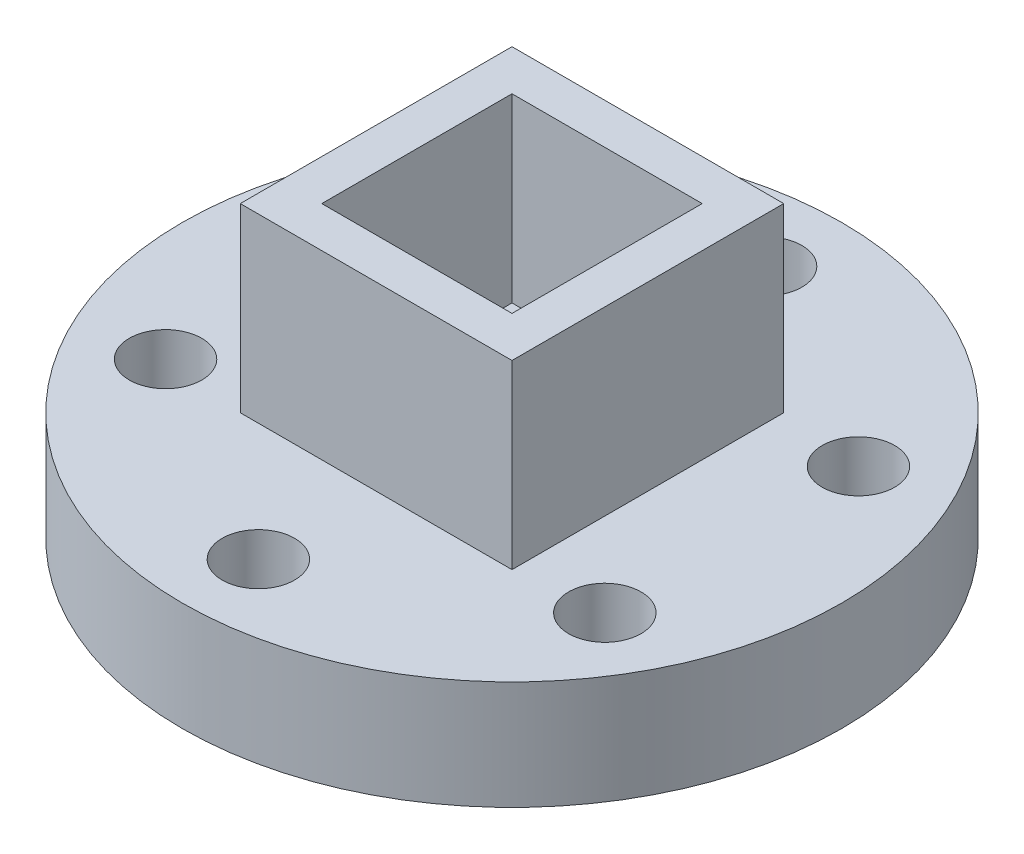
SolidWorks part; units mm, degrees
ref_plane "Front Plane" through (0, 0, 0) normal (0, 0, 1) x (1, 0, 0)
ref_plane "Top Plane" through (0, 0, 0) normal (0, 1, 0) x (1, 0, 0)
ref_plane "Right Plane" through (0, 0, 0) normal (1, 0, 0) x (0, 0, -1)
sketch "Sketch1" plane through (0, 0, 0) normal (0, 1, 0) x (1, 0, 0)
  circle A0 centre (0, 0) radius 18.2
  dimension "D1" = 36.4
extrude "Boss-Extrude1" add sketch "Sketch1" along normal blind 6 contours A0
sketch "Sketch2" plane through (0, 6, 0) normal (0, 1, 0) x (1, 0, 0)
  circle A0 centre (0, 14) radius 2
  circle A1 centre (12.1244, 7) radius 2
  circle A2 centre (12.1244, -7) radius 2
  circle A3 centre (0, -14) radius 2
  circle A4 centre (-12.1244, -7) radius 2
  circle A5 centre (-12.1244, 7) radius 2
  dimension "D1" = 14
  dimension "D2" = 6
extrude "Cut-Extrude1" cut sketch "Sketch2" against normal blind 6
sketch "Sketch3" plane through (0, 6, 0) normal (0, 1, 0) x (1, 0, 0)
  line L1 (-7.5, 7.5) -> (7.5, 7.5)
  line L2 (-7.5, 7.5) -> (-7.5, -7.5)
  line L3 (-7.5, -7.5) -> (7.5, -7.5)
  line L4 (7.5, 7.5) -> (7.5, -7.5)
  line L5 (-7.5, 7.5) -> (7.5, -7.5) construction
  line L6 (-7.5, -7.5) -> (7.5, 7.5) construction
  point P0 (0, 0)
extrude "Boss-Extrude2" add sketch "Sketch3" along normal blind 10
sketch "Sketch5" plane through (0, 16, 0) normal (0, 1, 0) x (1, 0, 0)
  line L1 (-5.25, 5.25) -> (5.25, 5.25)
  line L2 (-5.25, 5.25) -> (-5.25, -5.25)
  line L3 (-5.25, -5.25) -> (5.25, -5.25)
  line L4 (5.25, 5.25) -> (5.25, -5.25)
  line L5 (-5.25, 5.25) -> (5.25, -5.25) construction
  line L6 (-5.25, -5.25) -> (5.25, 5.25) construction
  point P0 (0, 0)
extrude "Cut-Extrude2" cut sketch "Sketch5" against normal blind 10
